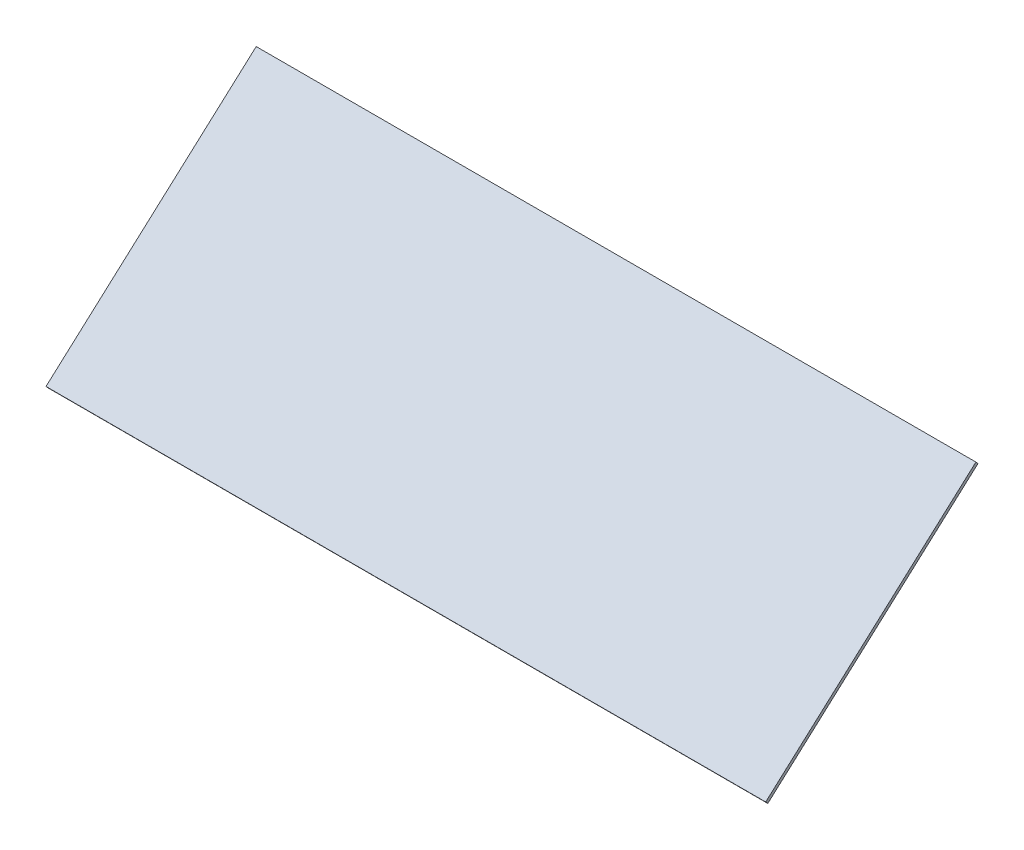
SolidWorks part; units mm, degrees
ref_plane "前视基准面" through (0, 0, 0) normal (0, 0, 1) x (1, 0, 0)
ref_plane "上视基准面" through (0, 0, 0) normal (0, 1, 0) x (1, 0, 0)
ref_plane "右视基准面" through (0, 0, 0) normal (1, 0, 0) x (0, 0, -1)
sketch "草图1" plane through (0, 0, 0) normal (1, 0, 0) x (0, 0, -1)
  line L1 (0, 0) -> (66.883, 60.2218)
  dimension "D2" = 90
base flange "基体-法兰1" sketch "草图1" end condition mid plane depth 229 reverse direction no thickness 1 reverse thickness direction no bend radius 0.7366
sketch "折弯-线1" plane through (0, 0, 0) normal (0, 1, 0) x (1, 0, 0)
sketch "边界框1" plane through (0, 0, 0) normal (0, 1, 0) x (1, 0, 0)
sheet metal parameters "钣金6" thickness 1 parameters "D1"=0.7366
flat pattern "平板型式6" [suppressed]
sketch "折弯-线2" plane through (0, 0, 0) normal (0, 1, 0) x (1, 0, 0)
sketch "边界框2" [suppressed] plane through (0, 0, 0) normal (0, 1, 0) x (1, 0, 0)
